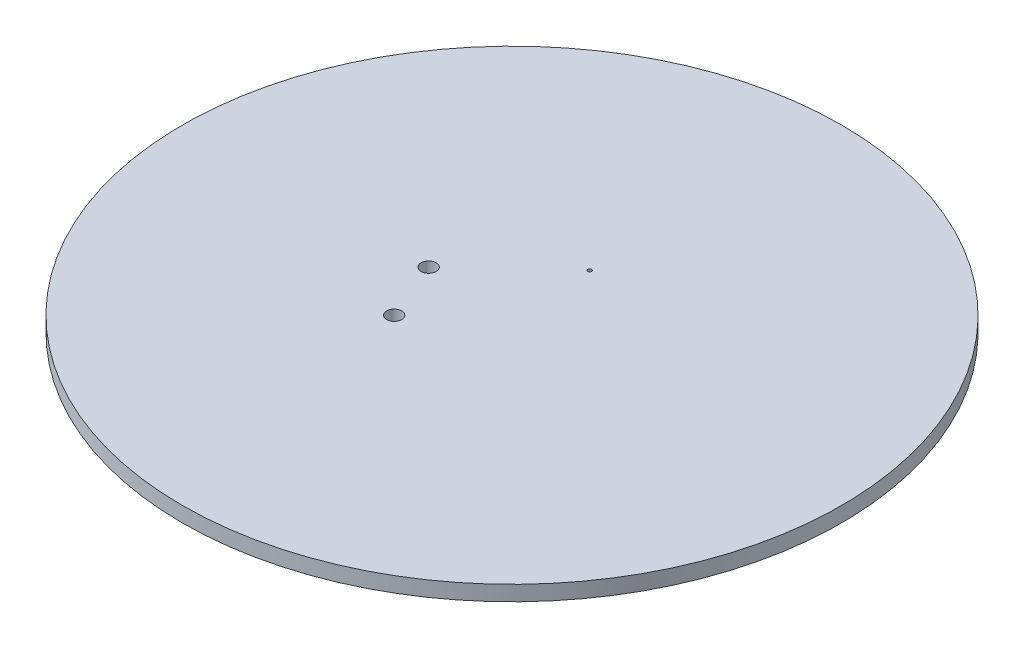
SolidWorks part; units mm, degrees
material "PTFE (general)"
ref_plane "Front Plane" through (0, 0, 0) normal (0, 0, 1) x (1, 0, 0)
ref_plane "Top Plane" through (0, 0, 0) normal (0, 1, 0) x (1, 0, 0)
ref_plane "Right Plane" through (0, 0, 0) normal (1, 0, 0) x (0, 0, -1)
sketch "Sketch1" plane through (0, 0, 0) normal (0, 1, 0) x (1, 0, 0)
  circle A0 centre (0, 0) radius 43.5
  dimension "D2" = 87
extrude "Boss-Extrude1" add sketch "Sketch1" along normal blind 2
sketch "Sketch2" plane through (0, 2, 0) normal (0, 1, 0) x (1, 0, 0)
  circle A0 centre (0, 10.25) radius 0.25
  dimension "D1" = 0.5
  dimension "D2" = 10.25
extrude "Cut-Extrude1" cut sketch "Sketch2" against normal through all both and the other way through all
sketch "Sketch3" plane through (0, 2, 0) normal (0, 1, 0) x (1, 0, 0)
  line L0 (0, 0) -> (-36.0536, 0) construction
  line L1 (0, 0) -> (0, 10.25) construction
  line L2 (0, 10.25) -> (0, 0) construction
  line L3 (0, 0) -> (-21.4265, -21.4265) construction
  circle A0 centre (-11, 0) radius 1
  circle A1 centre (-7.7782, -7.7782) radius 1
  dimension "D1" = 2
  dimension "D3" = 2
  dimension "D2" = 11
  dimension "D4" = 11
extrude "Cut-Extrude2" cut sketch "Sketch3" against normal through all both and the other way through all
